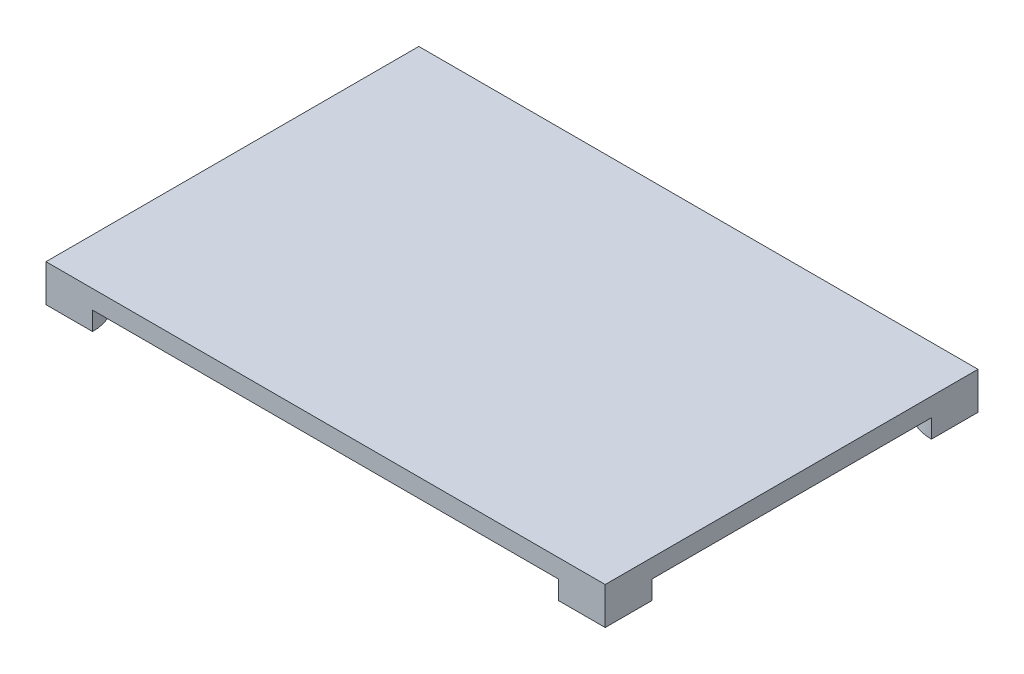
SolidWorks part; units mm, degrees
ref_plane "Ebene vorne" through (0, 0, 0) normal (0, 0, 1) x (1, 0, 0)
ref_plane "Ebene oben" through (0, 0, 0) normal (0, 1, 0) x (1, 0, 0)
ref_plane "Ebene rechts" through (0, 0, 0) normal (1, 0, 0) x (0, 0, -1)
sketch "Skizze1" plane through (0, 0, 0) normal (0, 1, 0) x (1, 0, 0)
  line L0 (0, 0) -> (60, 0)
  line L1 (-2.2, 0) -> (2.2, 0) construction
  line L2 (60, 0) -> (60, 40)
  line L3 (60, 40) -> (0, 40)
  line L4 (0, -2.2) -> (0, 2.2) construction
  line L5 (0, 40) -> (0, 0)
  dimension "D1" = 40
  dimension "D2" = 60
extrude "Aufsatz-Linear austragen1" add sketch "Skizze1" along normal blind 2
sketch "Skizze3" plane through (0, 0, 0) normal (0, 1, 0) x (1, 0, 0)
  line L0 (0, 0) -> (5, 0) construction
  line L1 (-2.2, 0) -> (2.2, 0) construction
  line L2 (0, -2.2) -> (0, 2.2) construction
  line L3 (0, 5) -> (0, 0) construction
  line L4 (60, 0) -> (55, 0)
  line L5 (60, 0) -> (60, 40) construction
  line L6 (60, 5) -> (60, 0)
  line L7 (0, 40) -> (5, 40)
  line L8 (60, 40) -> (0, 40) construction
  line L9 (0, 35) -> (0, 40)
  line L10 (60, 40) -> (55, 40)
  line L11 (60, 35) -> (60, 40)
  line L12 (0, 0) -> (5, 0)
  line L13 (0, 5) -> (0, 0)
  arc A0 (5, 0) -> (0, 5) centre (0, 0) ccw
  arc A1 (55, 0) -> (60, 5) centre (60, 0) cw
  arc A2 (5, 40) -> (0, 35) centre (0, 40) cw
  arc A3 (55, 40) -> (60, 35) centre (60, 40) ccw
  dimension "D1" = 5
  dimension "D2" = 5
  dimension "D3" = 5
  dimension "D4" = 5
  dimension "D5" = 5
  dimension "D6" = 5
  dimension "D7" = 5
  dimension "D8" = 5
extrude "Aufsatz-Linear austragen2" add sketch "Skizze3" against normal blind 2 from surface starting at face at (30, 0, -20)
